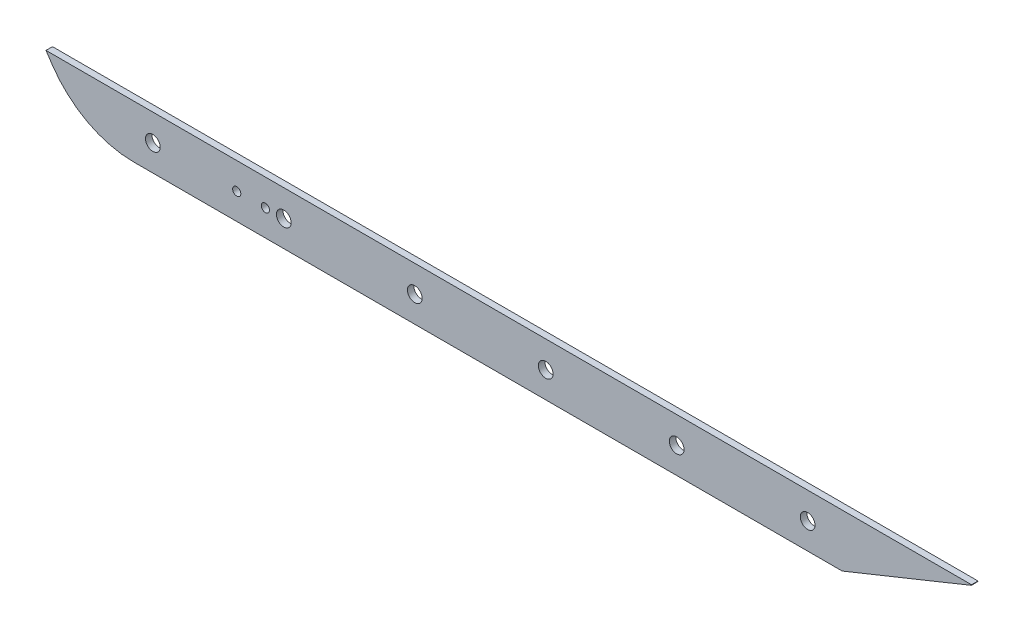
SolidWorks part; units mm, degrees
material "5052-H34"
ref_plane "Front Plane" through (0, 0, 0) normal (0, 0, 1) x (1, 0, 0)
ref_plane "Top Plane" through (0, 0, 0) normal (0, 1, 0) x (1, 0, 0)
ref_plane "Right Plane" through (0, 0, 0) normal (1, 0, 0) x (0, 0, -1)
sketch "Sketch1" plane through (0, 0, 0) normal (0, 0, 1) x (1, 0, 0)
  line L3 (428.1206, 28.9396) -> (0.5404, 28.9396)
  line L6 (-98.8794, 3.851) -> (-31.8794, -96.649)
  line L7 (428.1206, 28.9396) -> (403.1206, -71.149)
  line L9 (403.1206, -71.149) -> (366, -96.649)
  line L10 (-31.8794, -96.649) -> (366, -96.649)
  line L11 (0.5404, 28.9396) -> (-115.6052, 28.9396)
  line L12 (-98.8794, 3.851) -> (-115.6052, 28.9396)
  line L13 (-49.0861, -70.839) -> (403.198, -70.839)
  circle A0 centre (3.1206, -83.899) radius 3.6
  circle A1 centre (67.1206, -83.899) radius 3.6
  circle A2 centre (131.1206, -83.899) radius 3.6
  circle A3 centre (195.1206, -83.899) radius 3.6
  circle A4 centre (259.1206, -83.899) radius 3.6
  circle A5 centre (323.1206, -83.899) radius 3.6
  point P0 (-48.8794, -71.149)
  point P2 (-31.8794, -96.649)
  point P8 (48, -83.899)
  point P9 (403.1206, -71.149)
  point P23 (-49.0861, -70.839)
  point P25 (403.198, -70.839)
  dimension "D2" = 64
  dimension "D4" = 64
  dimension "D1" = 25.5
  dimension "D3" = 75
  dimension "D5" = 25
  dimension "D6" = 80
  dimension "D7" = 527
  dimension "D8" = 180
  dimension "D9" = 64
  dimension "D10" = 64
  dimension "D11" = 64
  dimension "D12" = 123.69
  dimension "D13" = 12.75
  dimension "D14" = 25.81
  dimension "D15" = 25.81
extrude "Boss-Extrude1" add sketch "Sketch1" along normal blind 3.175 contours L3 L11 L12 L6 L10 L9 L7
extrude "Cut-Extrude1" cut sketch "Sketch1<4>" along normal through all contours A0 | A1 | A2 | A3 | A4 | A5 region at (3.1206, -83.899, 0)
sketch "Sketch1<4>" plane through (0, 0, 0) normal (0, 0, 1) x (1, 0, 0) same geometry as "Sketch1"
sketch "Sketch5" plane through (0, 0, 0) normal (0, 0, -1) x (-1, 0, 0)
  line L0 (48.8794, -71.149) -> (-14.2353, -96.649)
  line L1 (31.8794, -96.649) -> (-366, -96.649) construction
  line L2 (-14.2353, -96.649) -> (31.8794, -96.649)
  line L3 (31.8794, -96.649) -> (48.8794, -71.149)
  line L6 (-366, -96.649) -> (-403.1206, -71.149)
  line L7 (-403.1206, -71.149) -> (-352, -71.149)
  line L9 (-352, -71.149) -> (-326.5, -96.649)
  line L11 (-366, -96.649) -> (-326.5, -96.649)
  dimension "D1" = 22
  dimension "D2" = 45
extrude "Cut-Extrude2" [suppressed] cut sketch "Sketch5" against normal up to next
fillet "Fillet1" radius 48 1 edges at (-31.8794, -96.649, 1.5875)
sketch "Sketch7" plane through (0, 0, 3.175) normal (0, 0, 1) x (1, 0, 0)
  line L0 (403.1206, -71.149) -> (340.0059, -96.649)
  line L1 (-31.8794, -96.649) -> (366, -96.649) construction
  line L2 (340.0059, -96.649) -> (366, -96.649)
  line L3 (366, -96.649) -> (403.1206, -71.149)
  dimension "D1" = 22
extrude "Cut-Extrude3" cut sketch "Sketch7" against normal blind 10
sketch "Sketch9" plane through (0, 0, 0) normal (0, 0, -1) x (-1, 0, 0)
  line L0 (-403.1206, -71.149) -> (48.8794, -71.149)
  line L1 (48.8794, -71.149) -> (48.8794, -114.9143)
  line L2 (48.8794, -114.9143) -> (-403.1206, -114.9143)
  line L3 (-403.1206, -114.9143) -> (-403.1206, -71.149)
extrude "Cut-Extrude4" [suppressed] cut sketch "Sketch9" against normal blind 10
sketch "Sketch11" plane through (0, 0, 3.175) normal (0, 0, 1) x (1, 0, 0)
  line L0 (-49.0861, -70.839) -> (403.198, -70.839) construction
  line L1 (-49.0861, -70.839) -> (403.198, -70.839)
  line L3 (-115.6052, 28.9396) -> (428.1206, 28.9396)
  line L4 (428.1206, 28.9396) -> (403.198, -70.839)
  line L5 (-49.0861, -70.839) -> (-115.6052, 28.9396)
extrude "Cut-Extrude5" cut sketch "Sketch11" against normal blind 10
sketch "Sketch13" plane through (0, 0, 0) normal (0, 0, -1) x (-1, 0, 0)
  circle A0 centre (-58.1206, -83.8863) radius 2
  circle A1 centre (-44.1206, -83.8863) radius 2
extrude "Cut-Extrude6" cut sketch "Sketch13" against normal blind 10
